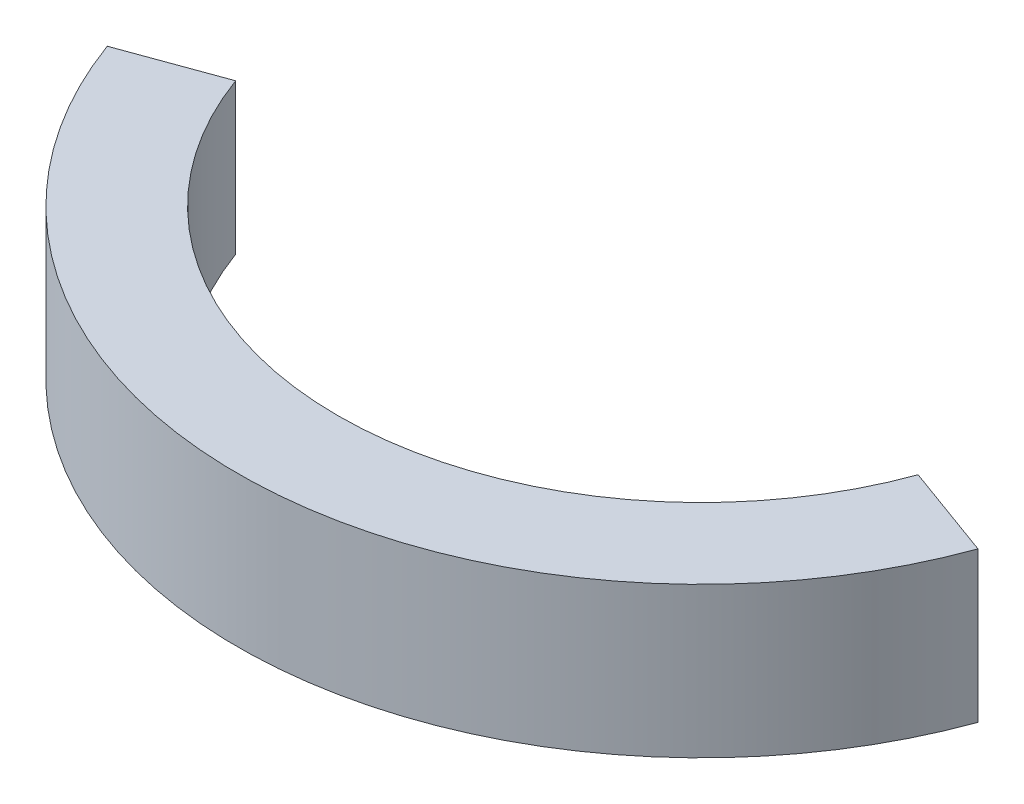
SolidWorks part; units mm, degrees
ref_plane "Front" through (0, 0, 0) normal (0, 0, 1) x (1, 0, 0)
ref_plane "Top" through (0, 0, 0) normal (0, 1, 0) x (1, 0, 0)
ref_plane "Right" through (0, 0, 0) normal (1, 0, 0) x (0, 0, -1)
sketch "Sketch1" plane through (0, 0, 0) normal (0, 1, 0) x (1, 0, 0)
  line L0 (-110.3904, -40.1788) -> (-86.5222, -31.4915)
  line L1 (86.5222, -31.4915) -> (110.3904, -40.1788)
  line L2 (-86.5222, -31.4915) -> (0, 0) construction
  line L3 (0, 0) -> (86.5222, -31.4915) construction
  line L4 (0, 0) -> (0, -117.475) construction
  line L5 (-86.5222, -31.4915) -> (0, -117.475) construction
  line L6 (0, -117.475) -> (86.5222, -31.4915) construction
  arc A0 (-110.3904, -40.1788) -> (110.3904, -40.1788) centre (0, 0) ccw
  arc A1 (-86.5222, -31.4915) -> (86.5222, -31.4915) centre (0, 0) ccw
  dimension "D1" = 25.4
  dimension "D2" = 117.475
  dimension "D3" = 140
extrude "Boss-Extrude1" add sketch "Sketch1" against normal blind 38.1
